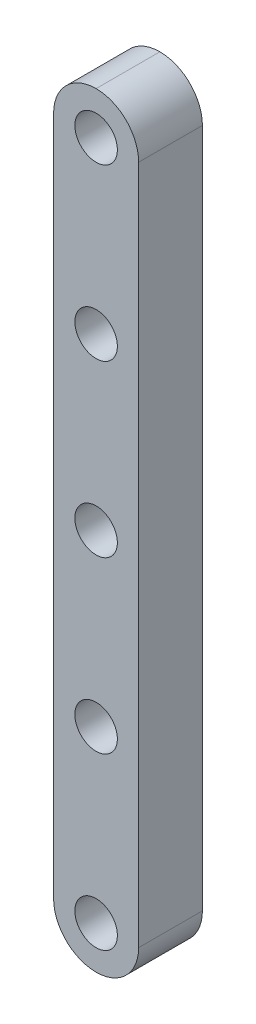
SolidWorks part; units mm, degrees
ref_plane "前视基准面" through (0, 0, 0) normal (0, 0, 1) x (1, 0, 0)
ref_plane "上视基准面" through (0, 0, 0) normal (0, 1, 0) x (1, 0, 0)
ref_plane "右视基准面" through (0, 0, 0) normal (1, 0, 0) x (0, 0, -1)
sketch "草图1" plane through (0, 0, 0) normal (0, 0, 1) x (1, 0, 0)
  line L0 (0, 0) -> (0, -80) construction
  line L1 (-10, -90) -> (10, -90)
  line L2 (-10, -90) -> (-10, 90)
  line L3 (-10, 90) -> (10, 90)
  line L4 (10, -90) -> (10, 90)
  line L5 (-10, -90) -> (10, 90) construction
  line L6 (-10, 90) -> (10, -90) construction
  line L7 (-10, 0) -> (10, 0) construction
  line L8 (0, -80) -> (0, 80) construction
  circle A0 centre (0, -80) radius 5
  circle A1 centre (0, 80) radius 5
  circle A2 centre (0, 0) radius 5
  circle A4 centre (0, -40) radius 5
  circle A5 centre (0, 40) radius 5
  point P0 (0, 0)
  dimension "D3" = 10
  dimension "D5" = 10
  dimension "D6" = 10
  dimension "D7" = 10
  dimension "D8" = 40
  dimension "D1" = 180
  dimension "D2" = 20
  dimension "D4" = 80
extrude "凸台-拉伸1" add sketch "草图1" along normal blind 15
fillet "圆角1" radius 10 4 edges at (-10, -90, 7.5) (10, -90, 7.5) (10, 90, 7.5) (-10, 90, 7.5)
